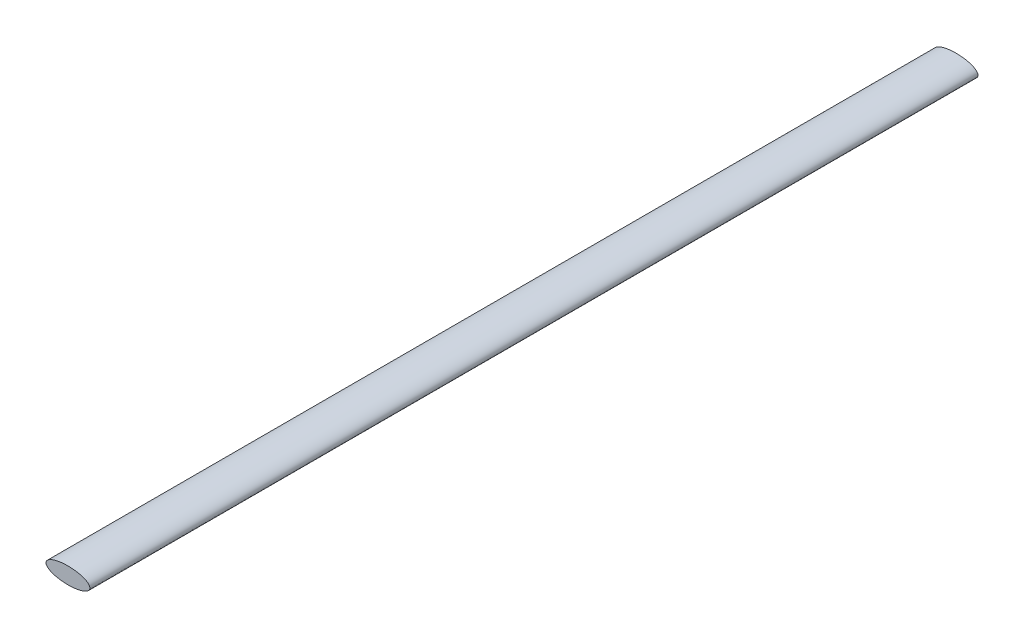
SolidWorks part; units mm, degrees
ref_plane "Front Plane" through (0, 0, 0) normal (0, 0, 1) x (1, 0, 0)
ref_plane "Top Plane" through (0, 0, 0) normal (0, 1, 0) x (1, 0, 0)
ref_plane "Right Plane" through (0, 0, 0) normal (1, 0, 0) x (0, 0, -1)
sketch "Sketch1" plane through (0, 0, 0) normal (0, 0, 1) x (1, 0, 0)
  ellipse E0 centre (0, 0) end of major axis (67.7799, 0) minor radius 25.3619
  point P1 (0, 0)
  point P7 (0, 0)
  point P9 (0, -25.3619)
  dimension "D1" = 67.7799
  dimension "D2" = 25.3619
extrude "Boss-Extrude2" add sketch "Sketch1" along normal blind 2743.2
